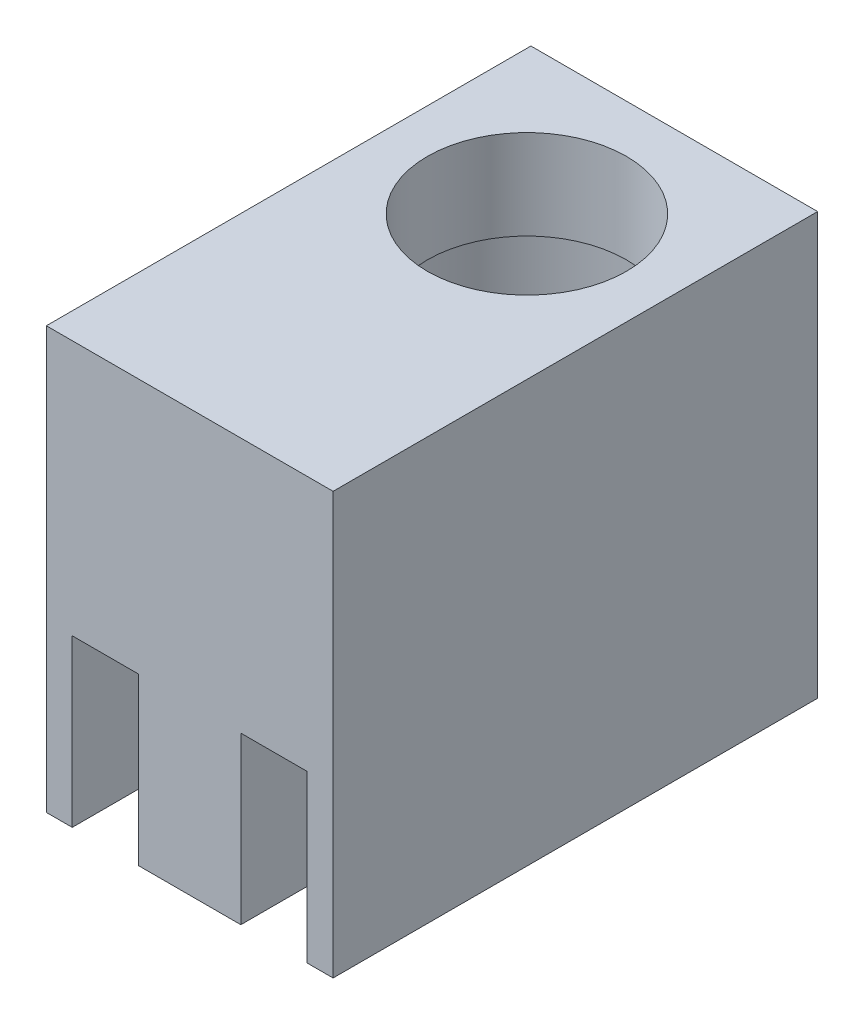
SolidWorks part; units mm, degrees
ref_plane "Спереди" through (0, 0, 0) normal (0, 0, 1) x (1, 0, 0)
ref_plane "Сверху" through (0, 0, 0) normal (0, 1, 0) x (1, 0, 0)
ref_plane "Справа" through (0, 0, 0) normal (1, 0, 0) x (0, 0, -1)
other "Configuration Table"
sketch "Эскиз1" plane through (0, 0, 0) normal (0, 1, 0) x (1, 0, 0)
  line L1 (2.16, -3.65) -> (-2.16, -3.65)
  line L2 (2.16, -3.65) -> (2.16, 3.65)
  line L3 (2.16, 3.65) -> (-2.16, 3.65)
  line L4 (-2.16, -3.65) -> (-2.16, 3.65)
  line L5 (2.16, -3.65) -> (-2.16, 3.65) construction
  line L6 (2.16, 3.65) -> (-2.16, -3.65) construction
  circle A0 centre (0, 1.43) radius 1.5
  circle A1 centre (0, 1.43) radius 2
  point P0 (0, 0)
  point P9 (0, 0.519)
  dimension "D3" = 3
  dimension "D4" = 4
  dimension "D1" = 4.32
  dimension "D2" = 7.3
  dimension "D5" = 5.08
extrude "Бобышка-Вытянуть2" add sketch "Эскиз1" along normal blind 6.35 contours L4 L1 L2 L3 A1 | A1 A0 region at (0, 0, 0.9473) region at (-1.9434, 0, -1.43)
extrude "Вырез-Вытянуть1" cut sketch "Эскиз1<4>" along normal blind 5 contours A1 A0 region at (-1.9434, 0, -1.43)
sketch "Эскиз1<4>" plane through (0, 0, 0) normal (0, 1, 0) x (1, 0, 0) same geometry as "Эскиз1"
sketch "Эскиз2" plane through (0, 0, 0) normal (0, -1, 0) x (1, 0, 0)
  line L0 (2.16, 3.65) -> (-2.16, 3.65) construction
  line L1 (-1.77, 3.65) -> (-0.77, 3.65)
  line L2 (-1.77, 3.65) -> (-1.77, -0.4988)
  line L3 (-1.77, -0.4988) -> (-0.77, -0.4988)
  line L4 (-0.77, 3.65) -> (-0.77, -0.4988)
  line L5 (-1.77, 3.65) -> (-0.77, -0.4988) construction
  line L6 (-1.77, -0.4988) -> (-0.77, 3.65) construction
  line L7 (0.77, 3.65) -> (1.77, 3.65)
  line L8 (0.77, 3.65) -> (0.77, -0.4988)
  line L9 (0.77, -0.4988) -> (1.77, -0.4988)
  line L10 (1.77, 3.65) -> (1.77, -0.4988)
  line L11 (0.77, 3.65) -> (1.77, -0.4988) construction
  line L12 (0.77, -0.4988) -> (1.77, 3.65) construction
  line L13 (-0.77, 3.65) -> (0.77, 3.65) construction
  circle A1 centre (0, -1.43) radius 2 construction
  point P0 (-0.77, 3.65)
  point P7 (-1.27, 3.65)
  point P8 (1.8879, 4.139)
  point P14 (-1.27, 1.5756)
  point P15 (1.27, 1.5756)
  point P16 (0, 3.65)
  dimension "D1" = 2.54
  dimension "D2" = 1
extrude "Вырез-Вытянуть2" cut sketch "Эскиз2" against normal blind 2.5
